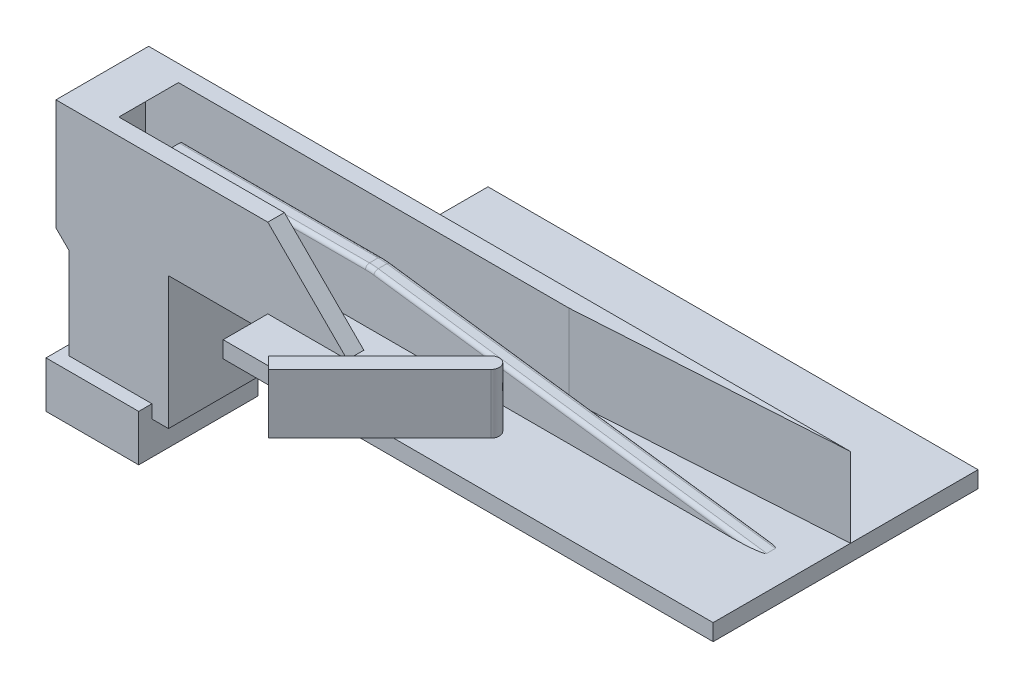
SolidWorks part; units mm, degrees
ref_plane "Front Plane" through (0, 0, 0) normal (0, 0, 1) x (1, 0, 0)
ref_plane "Top Plane" through (0, 0, 0) normal (0, 1, 0) x (1, 0, 0)
ref_plane "Right Plane" through (0, 0, 0) normal (1, 0, 0) x (0, 0, -1)
sketch "Sketch1" plane through (0, 0, 0) normal (0, 1, 0) x (1, 0, 0)
  line L1 (0, 0) -> (93.98, 0)
  line L2 (0, 0) -> (0, 50.8)
  line L3 (0, 50.8) -> (93.98, 50.8)
  line L4 (93.98, 0) -> (93.98, 50.8)
  dimension "D1" = 93.98
  dimension "D2" = 50.8
extrude "Boss-Extrude1" add sketch "Sketch1" along normal blind 3.175
ref_plane "Plane1" through (0, 0, -19.05) normal (0, 0, 1) x (1, 0, 0)
sketch "Sketch2" plane through (0, 0, -19.05) normal (0, 0, 1) x (1, 0, 0)
  line L0 (87.63, 3.175) -> (13.1271, 13.2211)
  line L1 (0, 3.175) -> (93.98, 3.175) construction
  line L2 (11.43, 13.335) -> (-26.67, 13.335)
  line L3 (-26.67, 13.335) -> (-26.67, 3.175)
  line L4 (-26.67, 3.175) -> (87.63, 3.175)
  arc A0 (11.43, 13.335) -> (13.1271, 13.2211) centre (11.43, 0.635) cw
  dimension "D3" = 12.7
  dimension "D1" = 10.16
  dimension "D2" = 6.35
  dimension "D4" = 38.1
  dimension "D5" = 76.2
extrude "Boss-Extrude2" add sketch "Sketch2" along normal blind 3.175
fillet "Fillet1" radius 0.762 6 edges at (-7.62, 13.335, -19.05) (12.2805, 13.3065, -19.05) (-7.62, 13.335, -15.875) (12.2805, 13.3065, -15.875) (50.3786, 8.198, -19.05) (50.3786, 8.198, -15.875)
sketch "Sketch3" plane through (0, 3.175, 0) normal (0, 1, 0) x (1, 0, 0)
  line L0 (43.18, 10.4549) -> (40.9349, 12.7)
  line L1 (43.18, 10.4549) -> (20.7294, -11.9957)
  line L2 (40.9349, 12.7) -> (18.4843, -9.7506)
  line L3 (20.7294, -11.9957) -> (18.4843, -9.7506)
  line L4 (43.18, 10.4549) -> (18.4843, -9.7506) construction
  line L5 (40.9349, 12.7) -> (20.7294, -11.9957) construction
  line L6 (0, 15.875) -> (81.9278, 15.875) construction
  line L7 (93.98, 0) -> (93.98, 50.8) construction
  point P1 (30.8321, 0.3521)
  dimension "D1" = 45
  dimension "D2" = 3.175
  dimension "D3" = 3.175
  dimension "D4" = 31.75
  dimension "D5" = 50.8
extrude "Boss-Extrude3" add sketch "Sketch3" along normal blind 11.43
fillet "Fillet2" radius 1.6002 2 edges at (40.9349, 8.89, -12.7) (43.18, 8.89, -10.4549)
sketch "Sketch4" plane through (0, 0, 0) normal (-1, 0, 0) x (0, 0, 1)
  line L0 (-50.8, 0) -> (0, 0) construction
  line L1 (-11.7475, 0) -> (-23.1775, 0)
  line L2 (-11.7475, 3.175) -> (-11.7475, 18.415)
  line L3 (-11.7475, 18.415) -> (-23.1775, 18.415)
  line L4 (-23.1775, 3.175) -> (-23.1775, 18.415)
  line L5 (-15.875, 12.573) -> (-15.875, 3.175) construction
  line L6 (-8.5725, 0) -> (-26.3525, 0)
  line L7 (-8.5725, 0) -> (-8.5725, 18.415)
  line L9 (-26.3525, 0) -> (-26.3525, 18.415)
  line L10 (-50.8, 3.175) -> (-19.05, 3.175) construction
  line L11 (-23.1775, 3.175) -> (-11.7475, 3.175)
  line L12 (-15.875, 3.175) -> (0, 3.175) construction
  line L13 (-23.1775, 18.415) -> (-26.3525, 18.415)
  line L14 (-26.3525, 18.415) -> (-11.7475, 18.415)
  line L15 (-8.5725, 18.415) -> (-11.7475, 18.415)
  line L16 (-26.3525, 18.415) -> (-23.1775, 18.415)
  line L17 (-23.1775, 3.175) -> (-23.1775, 0)
  line L18 (-11.7475, 3.175) -> (-11.7475, 0)
  line M9 (-50.8, 0) -> (0, 0)
  line M11 (0, 3.175) -> (-15.875, 3.175)
  line M13 (-19.05, 3.175) -> (-50.8, 3.175)
  dimension "D1" = 11.43
  dimension "D2" = 4.1275
  dimension "D3" = 3.175
  dimension "D4" = 3.175
  dimension "D6" = 15.24
extrude "Boss-Extrude4" add sketch "Sketch4" along normal blind 38.1 contours L4 L13 L9 M13 | L7 L15 L2 M11 | L18 L7 M11 M9 | L17 L9 M13 M9 region at (0, 1.5875, -10.16) region at (0, 1.5875, -24.765) region at (0, 10.795, -10.16) region at (0, 10.795, -24.765)
chamfer "Chamfer1" distance 15.24 angle 45 2 edges at (0, 3.175, -10.16) (0, 3.175, -24.765)
sketch "Sketch8" plane through (0, 0, 0) normal (0, -1, 0) x (1, 0, 0)
  line L0 (-38.1, -8.5725) -> (0, -8.5725) construction
  line L1 (-38.1, -26.3525) -> (-19.05, -26.3525)
  line L2 (-38.1, -26.3525) -> (-38.1, -8.5725)
  line L3 (-38.1, -8.5725) -> (-19.05, -8.5725)
  line L4 (-19.05, -26.3525) -> (-19.05, -8.5725)
  dimension "D1" = 19.05
extrude "Boss-Extrude5" add sketch "Sketch8" along normal blind 25.4
sketch "Sketch9" plane through (0, 0, 0) normal (0, 1, 0) x (1, 0, 0)
  line L1 (-34.925, 23.1775) -> (-27.305, 23.1775)
  line L2 (-34.925, 23.1775) -> (-34.925, 11.7475)
  line L3 (-34.925, 11.7475) -> (-27.305, 11.7475)
  line L4 (-27.305, 23.1775) -> (-27.305, 11.7475)
  line L7 (-38.1, 11.7475) -> (-38.1, 23.1775) construction
  point P8 (-27.305, 17.4625)
  dimension "D1" = 7.62
  dimension "D2" = 3.175
extrude "Cut-Extrude3" cut sketch "Sketch9" against normal through all
chamfer "Chamfer2" distance 3.175 distance2 25.4 2 edges at (-27.305, 0, -17.4625) (-34.925, 0, -17.4625) first distance on face at (-23.1775, 0, -17.4625) first distance on face at (-36.5125, 0, -17.4625)
sketch "Sketch10" plane through (0, -25.4, 0) normal (0, -1, 0) x (1, 0, 0)
  line L1 (-37.465, -8.5725) -> (-24.765, -8.5725)
  line L2 (-37.465, -8.5725) -> (-37.465, -26.3525)
  line L3 (-37.465, -26.3525) -> (-24.765, -26.3525)
  line L4 (-24.765, -8.5725) -> (-24.765, -26.3525)
  line L5 (-27.305, -11.7475) -> (-27.305, -23.1775) construction
  line L6 (-34.925, -11.7475) -> (-27.305, -11.7475) construction
  line L8 (-22.225, -28.8925) -> (-40.005, -28.8925)
  line L9 (-22.225, -28.8925) -> (-22.225, -6.0325)
  line L10 (-22.225, -6.0325) -> (-40.005, -6.0325)
  line L11 (-40.005, -28.8925) -> (-40.005, -6.0325)
  point P12 (-31.115, -8.5725)
  dimension "D1" = 12.7
  dimension "D2" = 17.78
  dimension "D3" = 2.54
  dimension "D4" = 3.175
  dimension "D5" = 2.54
  dimension "D6" = 2.54
  dimension "D7" = 2.54
  dimension "D8" = 2.54
sketch "Sketch14" plane through (0, -25.4, 0) normal (0, -1, 0) x (1, 0, 0)
  line L1 (-22.225, -6.0325) -> (-40.005, -6.0325)
  line L2 (-22.225, -6.0325) -> (-22.225, -28.8925)
  line L3 (-22.225, -28.8925) -> (-40.005, -28.8925)
  line L4 (-40.005, -6.0325) -> (-40.005, -28.8925)
  line L5 (-27.305, -11.7475) -> (-34.925, -11.7475)
  line L6 (-27.305, -11.7475) -> (-27.305, -23.1775)
  line L7 (-27.305, -23.1775) -> (-34.925, -23.1775)
  line L8 (-34.925, -11.7475) -> (-34.925, -23.1775)
extrude "Boss-Extrude11" add sketch "Sketch14" against normal blind 2.54
extrude "Boss-Extrude12" add sketch "Sketch10" along normal blind 6.35
sketch "Sketch11" plane through (0, 0, -11.7475) normal (0, 0, -1) x (-1, 0, 0)
  line L1 (38.1, 18.415) -> (31.75, 18.415)
  line L2 (38.1, 18.415) -> (38.1, 15.24)
  line L3 (38.1, 15.24) -> (31.75, 15.24)
  line L4 (31.75, 18.415) -> (31.75, 15.24)
  dimension "D1" = 6.35
  dimension "D2" = 3.175
extrude "Boss-Extrude7" add sketch "Sketch11" along normal up to surface (14.605 mm away) up to face at (-14.351, -5.334, -26.3525)
chamfer "Chamfer3" distance 3.175 angle 45 1 edges at (-31.75, 15.24, -17.4625)
sketch "Sketch13" plane through (-38.1, 0, 0) normal (-1, 0, 0) x (0, 0, 1)
  line L0 (-8.5725, -22.86) -> (-8.5725, 18.415) construction
  line L1 (-26.3525, 18.415) -> (-8.5725, 18.415)
  line L2 (-26.3525, 18.415) -> (-26.3525, -2.2225)
  line L3 (-26.3525, -2.2225) -> (-8.5725, -2.2225)
  line L4 (-8.5725, 18.415) -> (-8.5725, -2.2225)
extrude "Boss-Extrude8" add sketch "Sketch13" along normal blind 2.54
chamfer "Chamfer4" distance 3.175 angle 45 1 edges at (-38.1, -2.2225, -17.4625)
sketch "Sketch15" plane through (0, 0, -26.3525) normal (0, 0, -1) x (-1, 0, 0)
  line L1 (0, 18.415) -> (-93.98, 18.415)
  line L2 (0, 18.415) -> (0, 3.175)
  line L3 (0, 3.175) -> (-93.98, 3.175)
  line L4 (-93.98, 18.415) -> (-93.98, 3.175)
extrude "Boss-Extrude13" add sketch "Sketch15" against normal up to surface (3.175 mm away) up to face at (-22.3441, -4.2862, -23.1775)
chamfer "Chamfer5" distance 3.175 distance2 50.8 1 edges at (93.98, 10.795, -23.1775) first distance on face at (93.98, 6.1913, -25.0825)
ref_plane "Plane2" through (-26.67, 3.175, -19.05) normal (1, 0, 0) x (0, 0, -1)
sketch "Sketch17" plane through (0, 3.175, 0) normal (0, -1, 0) x (1, 0, 0)
  line L0 (-26.67, -26.3842) -> (-26.67, -11.7158) construction
  line L1 (0, -26.3525) -> (-26.67, -26.3525)
  line L2 (0, -26.3525) -> (0, -11.7475)
  line L3 (0, -11.7475) -> (-26.67, -11.7475)
  line L4 (-26.67, -26.3525) -> (-26.67, -11.7475)
extrude "Boss-Extrude14" add sketch "Sketch17" along normal blind 3.175
